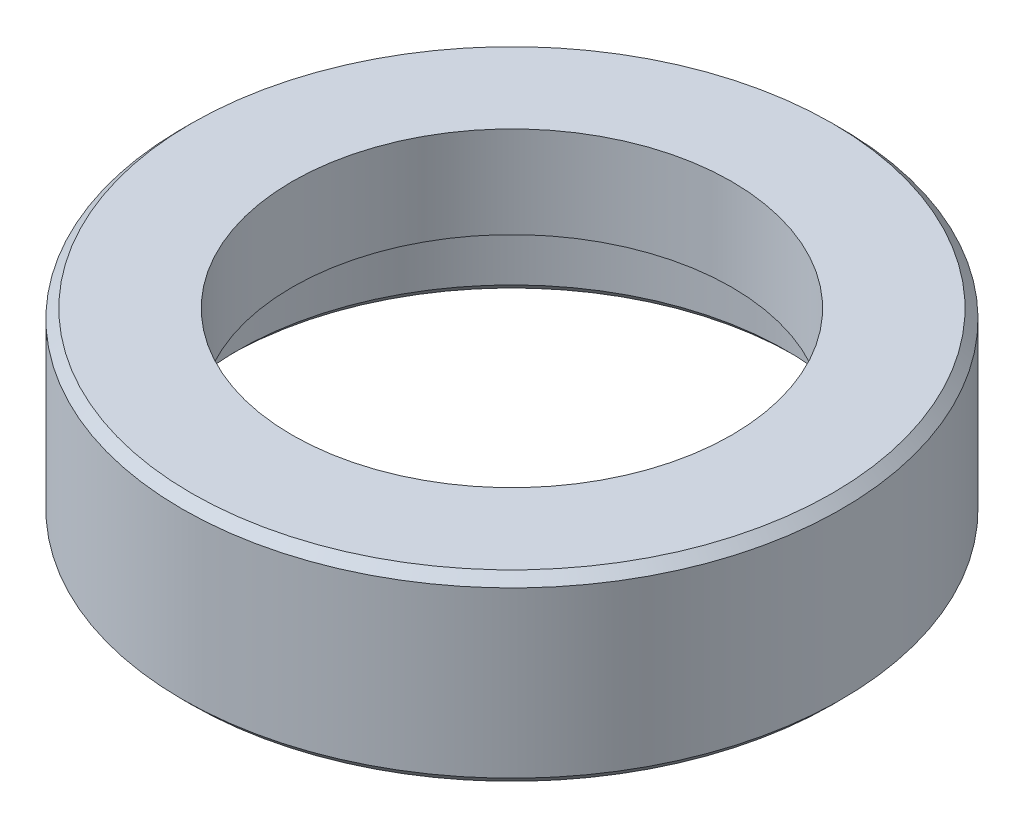
SolidWorks part; units mm, degrees
material "AISI 1045 Steel, cold drawn"
ref_plane "Front Plane" through (0, 0, 0) normal (0, 0, 1) x (1, 0, 0)
ref_plane "Top Plane" through (0, 0, 0) normal (0, 1, 0) x (1, 0, 0)
ref_plane "Right Plane" through (0, 0, 0) normal (1, 0, 0) x (0, 0, -1)
sketch "Sketch1" plane through (0, 0, 0) normal (0, 1, 0) x (1, 0, 0)
  circle A0 centre (0, 0) radius 6
  circle A1 centre (0, 0) radius 7.5
  circle A2 centre (0, 0) radius 9
extrude "Boss-Extrude1" add sketch "Sketch1" along normal blind 5 contours A2
extrude "Cut-Extrude1" cut sketch "Sketch1<3>" along normal up to surface (5 mm away) contours A0 region at (0, 0, 0) up to face at (0, 5, 9)
sketch "Sketch1<3>" plane through (0, 0, 0) normal (0, 1, 0) x (1, 0, 0) same geometry as "Sketch1"
extrude "Cut-Extrude2" cut sketch "Sketch1<4>" along normal blind 2.5 contours A1 A0 region at (-7.2879, 0, 0)
sketch "Sketch1<4>" plane through (0, 0, 0) normal (0, 1, 0) x (1, 0, 0) same geometry as "Sketch1"
chamfer "Chamfer1" distance 0.25 angle 45 3 edges at (0, 0, 7.5) (0, 0, 9) (0, 5, 9)
